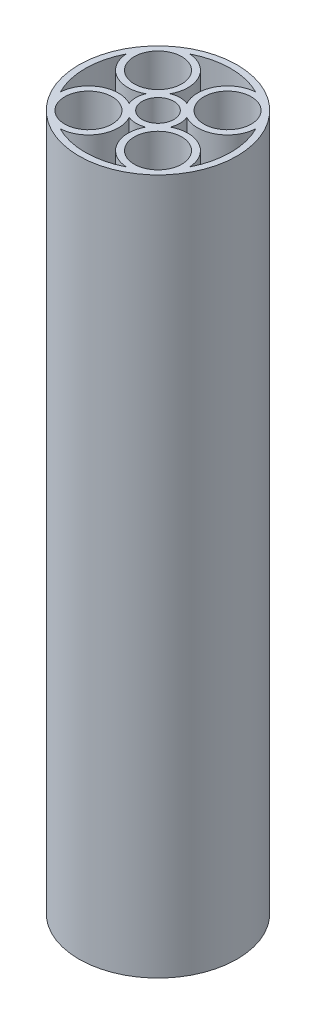
SolidWorks part; units mm, degrees
material "Stainless Steel 2205"
ref_plane "Front Plane" through (0, 0, 0) normal (0, 0, 1) x (1, 0, 0)
ref_plane "Top Plane" through (0, 0, 0) normal (0, 1, 0) x (1, 0, 0)
ref_plane "Right Plane" through (0, 0, 0) normal (1, 0, 0) x (0, 0, -1)
sketch "Sketch1" plane through (0, 0, 0) normal (0, 1, 0) x (1, 0, 0)
  circle A0 centre (0, 0) radius 125
  circle A1 centre (55, 55) radius 37.5
  circle A2 centre (55, -55) radius 37.5
  circle A3 centre (-55, -55) radius 37.5
  circle A4 centre (-55, 55) radius 37.5
  circle A5 centre (0, 0) radius 25
  point P14 (0, 0)
  dimension "D1" = 75
  dimension "D6" = 250
  dimension "D7" = 50
  dimension "D3" = 55
  dimension "D4" = 55
  dimension "D5" = 110
  dimension "D2" = 4
extrude "Boss-Extrude1" add sketch "Sketch1" against normal blind 1050
sketch "Sketch2" plane through (0, -1050, 0) normal (0, -1, 0) x (1, 0, 0)
  circle A0 centre (0, 0) radius 125
  circle A1 centre (0, 0) radius 25
extrude "Boss-Extrude2" add sketch "Sketch2" along normal blind 50
shell "Shell1" thickness 10 removed face at (-55, 0, -17.5)
